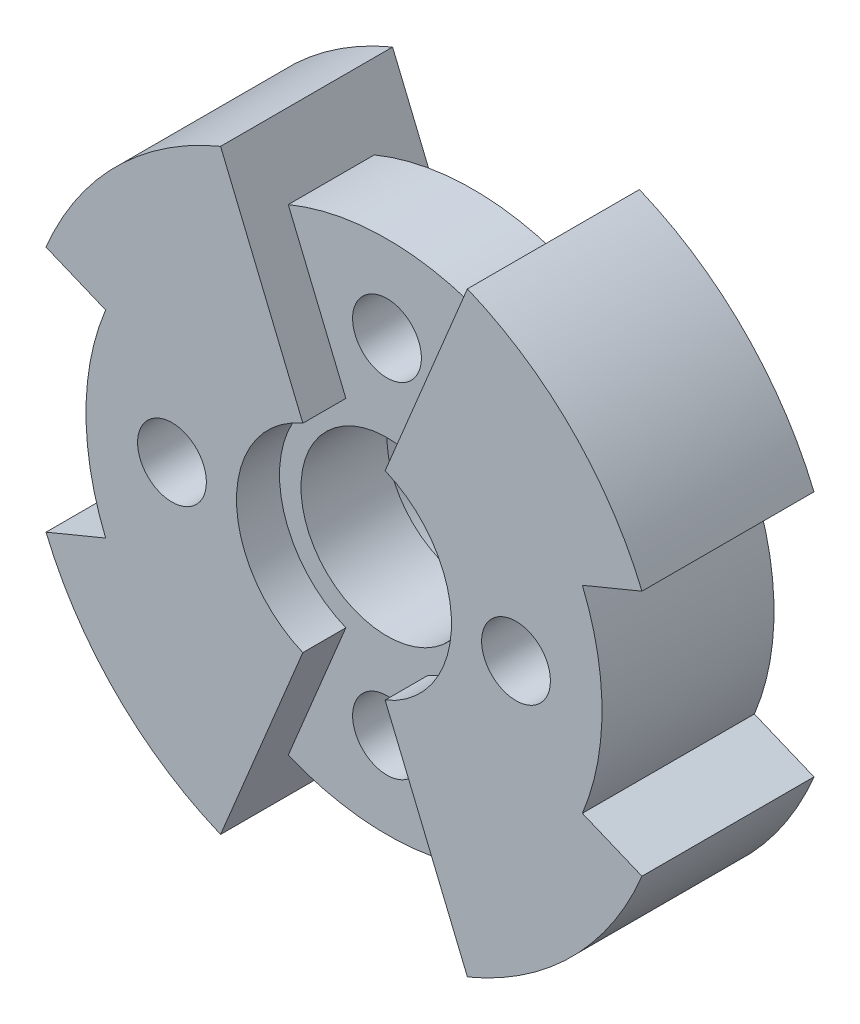
SolidWorks part; units mm, degrees
ref_plane "Front Plane" through (0, 0, 0) normal (0, 0, 1) x (1, 0, 0)
ref_plane "Top Plane" through (0, 0, 0) normal (0, 1, 0) x (1, 0, 0)
ref_plane "Right Plane" through (0, 0, 0) normal (1, 0, 0) x (0, 0, -1)
sketch "Sketch1" plane through (0, 0, 0) normal (0, 0, 1) x (1, 0, 0)
  line L0 (0, 2345.245) -> (0, -2047.6251) construction
  line L1 (-3744.0586, 0) -> (3613.1058, 0) construction
  line L2 (1407.9924, 583.2096) -> (1759.9905, 729.0119)
  line L3 (1407.9924, -583.2096) -> (1759.9905, -729.0119)
  line L4 (-1407.9924, -583.2096) -> (-1759.9905, -729.0119)
  line L5 (-1407.9924, 583.2096) -> (-1759.9905, 729.0119)
  line L6 (-243.004, 586.6635) -> (-729.0119, 1759.9905)
  line L7 (243.004, 586.6635) -> (729.0119, 1759.9905)
  line L8 (243.004, -586.6635) -> (729.0119, -1759.9905)
  line L9 (-243.004, -586.6635) -> (-729.0119, -1759.9905)
  arc A0 (1759.9905, 729.0119) -> (729.0119, 1759.9905) centre (0, 0) ccw
  circle A1 centre (0, 0) radius 1524
  arc A2 (-1759.9905, -729.0119) -> (-729.0119, -1759.9905) centre (0, 0) ccw
  circle A3 centre (0, 0) radius 508
  circle A4 centre (0, 0) radius 635
  circle A5 centre (0, 0) radius 1016 construction
  circle A6 centre (0, 1016) radius 203.2
  circle A7 centre (1016, 0) radius 203.2
  circle A8 centre (0, -1016) radius 203.2
  circle A9 centre (-1016, 0) radius 203.2
  arc A10 (729.0119, -1759.9905) -> (1759.9905, -729.0119) centre (0, 0) ccw
  arc A11 (-729.0119, 1759.9905) -> (-1759.9905, 729.0119) centre (0, 0) ccw
  point P29 (0, 0)
  dimension "D1" = 3810
  dimension "D2" = 3048
  dimension "D4" = 1016
  dimension "D5" = 1270
  dimension "D6" = 2032
  dimension "D7" = 406.4
  dimension "D3" = 22.5
  dimension "D9" = 22.5
  dimension "D8" = 4
extrude "Boss-Extrude1" add sketch "Sketch1" along normal mid plane 1016 contours L6 A11 L5 A1 | A4 L6 A1 L9 A9 | L4 A2 L9 A1 | A1 L2 A0 L7 | A4 L8 A1 L7 A7 | L8 A10 L3 A1 region at (1186.2762, 1186.2762, 0) region at (1464.3746, 291.2822, 0) region at (1186.2762, -1186.2762, 0) region at (-1186.2762, 1186.2762, 0) region at (-441.6884, 985.489, 0) region at (-1186.2762, -1186.2762, 0)
extrude "Boss-Extrude2" add sketch "Sketch1<3>" along normal mid plane 508 contours A4 A3 | A4 L7 A1 L6 A6 | A4 L9 A1 L8 A8 region at (399.2821, 1003.0543, 0) region at (513.0496, 342.8088, 0) region at (0, -1509.0363, 0)
sketch "Sketch1<3>" plane through (0, 0, 0) normal (0, 0, 1) x (1, 0, 0) same geometry as "Sketch1"
